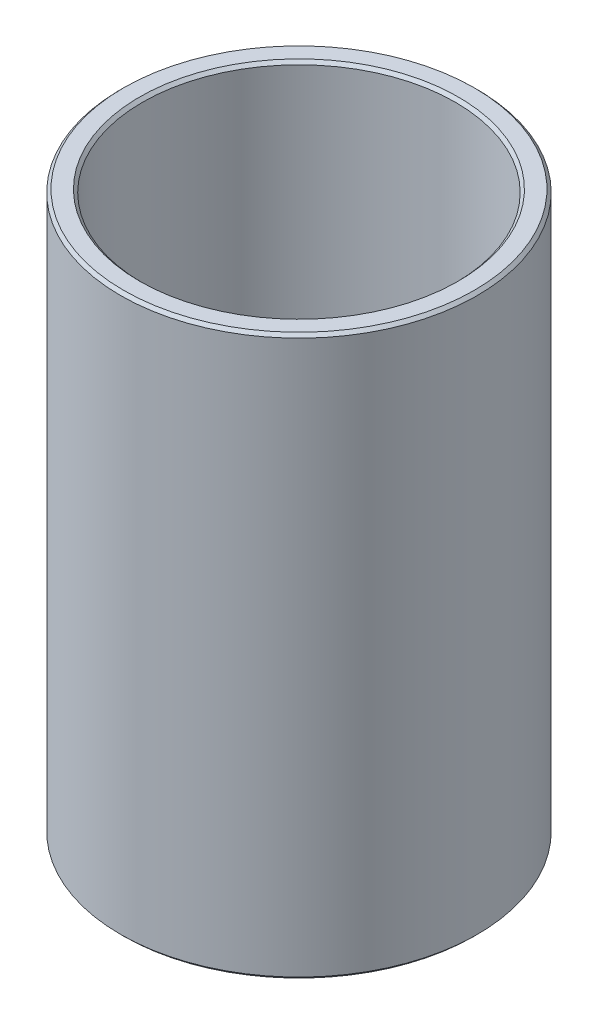
SolidWorks part; units mm, degrees
ref_plane "Front Plane" through (0, 0, 0) normal (0, 0, 1) x (1, 0, 0)
ref_plane "Top Plane" through (0, 0, 0) normal (0, 1, 0) x (1, 0, 0)
ref_plane "Right Plane" through (0, 0, 0) normal (1, 0, 0) x (0, 0, -1)
sketch "Sketch1" plane through (0, 0, 0) normal (0, 1, 0) x (1, 0, 0)
  circle A0 centre (0, 0) radius 32.5
  dimension "SLEEVE_OD" = 65
extrude "Boss-Extrude1" add sketch "Sketch1" along normal blind 101.9047
sketch "Sketch2" plane through (0, 0, 0) normal (0, 1, 0) x (1, 0, 0)
  circle A0 centre (0, 0) radius 28.5052
  dimension "BORE_D" = 57.0104
extrude "Cut-Extrude1" cut sketch "Sketch2" along normal through all
chamfer "Chamfer1" distance 0.5482 angle 45 4 edges at (0, 101.9047, 28.5052) (0, 0, 28.5052) (0, 0, 32.5) (0, 101.9047, 32.5)
